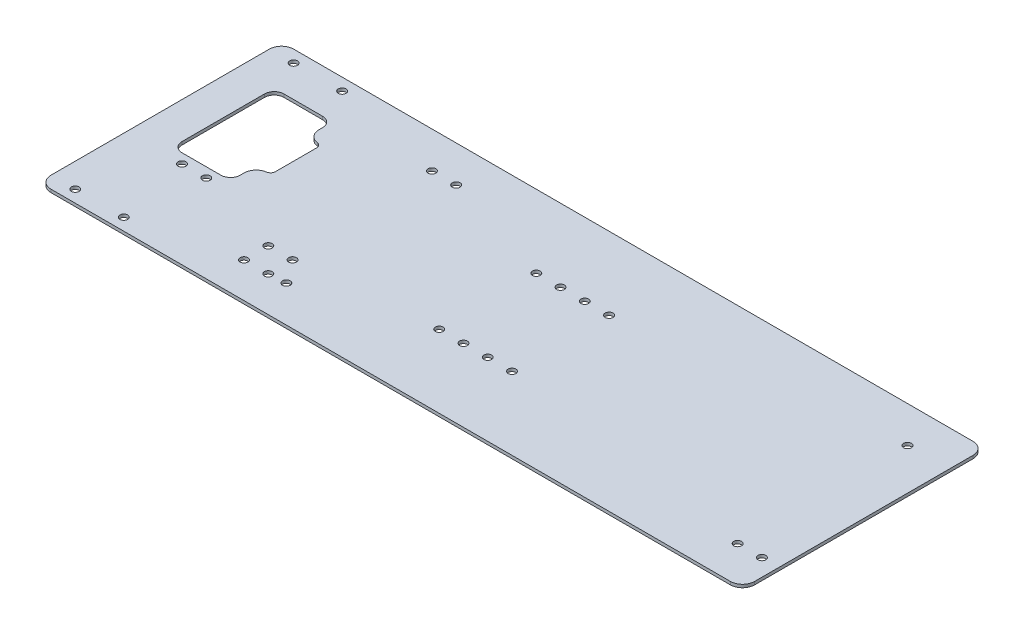
SolidWorks part; units mm, degrees
ref_plane "Front Plane" through (0, 0, 0) normal (0, 0, 1) x (1, 0, 0)
ref_plane "Top Plane" through (0, 0, 0) normal (0, 1, 0) x (1, 0, 0)
ref_plane "Right Plane" through (0, 0, 0) normal (1, 0, 0) x (0, 0, -1)
sketch "Sketch1" plane through (0, 0, 0) normal (0, 1, 0) x (1, 0, 0)
  line L0 (128.27, 0) -> (-128.27, 0) construction
  line L1 (184.15, 63.5) -> (-184.15, 63.5)
  line L2 (184.15, 63.5) -> (184.15, -63.5)
  line L3 (184.15, -63.5) -> (-184.15, -63.5)
  line L4 (-184.15, 63.5) -> (-184.15, -63.5)
  line L5 (184.15, 63.5) -> (-184.15, -63.5) construction
  line L6 (184.15, -63.5) -> (-184.15, 63.5) construction
  line L7 (-128.27, 0) -> (-128.27, 31.75) construction
  line L8 (-128.27, 31.75) -> (-134.62, 31.75) construction
  line L9 (-128.27, 6.35) -> (-134.62, 6.35) construction
  line L12 (-165.1, -12.7) -> (-165.1, 40.64)
  line L15 (-134.62, -12.7) -> (-165.1, -12.7)
  line L17 (-134.62, 40.64) -> (-165.1, 40.64)
  line L18 (0, 63.5) -> (0, -63.5) construction
  line L19 (-134.62, 40.64) -> (-134.62, -12.7)
  line L21 (-95.25, -45.0215) -> (-95.25, -32.3215) construction
  line L22 (-82.55, -45.0215) -> (-95.25, -45.0215) construction
  line L25 (128.27, 31.75) -> (128.27, 6.35) construction
  line L26 (-95.25, -32.3215) -> (-82.55, -32.3215) construction
  line L30 (-82.55, -32.3215) -> (-82.55, -45.0215) construction
  line L31 (184.15, -17.78) -> (154.94, -17.78) construction
  line L32 (146.05, 57.15) -> (184.15, 57.15) construction
  line L33 (154.94, -17.78) -> (142.24, -17.78) construction
  line L34 (146.05, -57.15) -> (184.15, -57.15) construction
  line L35 (-146.05, -57.15) -> (-184.15, -57.15) construction
  line L36 (-146.05, 57.15) -> (-184.15, 57.15) construction
  line L37 (-128.27, 0) -> (-128.27, 6.35) construction
  line L38 (-184.15, -17.78) -> (-154.94, -17.78) construction
  line L39 (-154.94, -17.78) -> (-142.24, -17.78) construction
  line L40 (-134.62, 27.305) -> (-127, 27.305)
  line L41 (-127, 27.305) -> (-127, 0.635)
  line L42 (-127, 0.635) -> (-134.62, 0.635)
  circle A4 centre (171.45, 31.75) radius 2.032 construction
  circle A5 centre (128.27, 31.75) radius 2.032 construction
  circle A6 centre (128.27, 6.35) radius 2.032 construction
  circle A7 centre (171.45, -3.81) radius 2.032 construction
  circle A8 centre (171.45, -57.15) radius 2.032
  circle A9 centre (146.05, -57.15) radius 2.032
  circle A10 centre (171.45, 57.15) radius 2.032
  circle A11 centre (146.05, 57.15) radius 2.032
  circle A12 centre (-146.05, -57.15) radius 2.032
  circle A13 centre (-171.45, -57.15) radius 2.032
  circle A14 centre (-146.05, 57.15) radius 2.032
  circle A15 centre (-171.45, 57.15) radius 2.032
  circle A16 centre (142.24, -17.78) radius 2.032 construction
  circle A17 centre (154.94, -17.78) radius 2.032 construction
  circle A18 centre (-154.94, -17.78) radius 2.032
  circle A19 centre (-142.24, -17.78) radius 2.032
  circle A20 centre (-95.25, -45.0215) radius 2.032
  circle A21 centre (-82.55, -45.0215) radius 2.032
  circle A22 centre (-95.25, -32.3215) radius 2.032
  circle A23 centre (-82.55, -32.3215) radius 2.032
  point P0 (0, 0)
  point P11 (-128.27, 0)
  point P13 (-134.62, 31.75)
  point P17 (-134.62, 6.35)
  point P37 (0, 0)
  point P50 (171.45, 57.15)
  point P51 (146.05, 57.15)
  point P56 (171.45, -57.15)
  point P57 (146.05, -57.15)
  point P84 (-130.81, 27.305)
  point P87 (130.81, 27.305)
  dimension "D5" = 13.335
  dimension "D18" = 4.064
  dimension "D1" = 368.3
  dimension "D2" = 127
  dimension "D3" = 128.27
  dimension "D4" = 25.4
  dimension "D7" = 6.35
  dimension "D8" = 30.48
  dimension "D9" = 53.34
  dimension "D10" = 8.89
  dimension "D11" = 19.05
  dimension "D14" = 12.7
  dimension "D15" = 38.1
  dimension "D16" = 12.7
  dimension "D17" = 38.1
  dimension "D19" = 31.75
  dimension "D20" = 6.35
  dimension "D21" = 6.35
  dimension "D22" = 5.08
  dimension "D23" = 29.21
  dimension "D24" = 12.7
  dimension "D25" = 88.9
  dimension "D26" = 12.7
  dimension "D27" = 7.62
  dimension "D28" = 26.67
  dimension "D29" = 13.335
  dimension "D30" = 18.4785
  dimension "D31" = 12.7
extrude "Boss-Extrude1" add sketch "Sketch1" along normal blind 1.5875 contours L1 L4 L3 L2 A18 A17 A16 A14 A12 A11 A10 A9 A8 L41 L42 L19 L15 L12 L17 L40 A13 A15 A19 | A9 | A8 | A10 | A11 region at (6.2259, 0, 0.5157)
sketch "Sketch2" [suppressed] plane through (0, 1.5875, 0) normal (0, 1, 0) x (1, 0, 0)
  line L0 (-69.85, 63.5) -> (-69.85, -63.5)
  line L1 (184.15, 63.5) -> (-184.15, 63.5) construction
  line L2 (184.15, -63.5) -> (-184.15, -63.5) construction
  circle A0 centre (-82.55, -45.0215) radius 2.032 construction
  circle M9 centre (146.05, 57.15) radius 2.032
  circle M10 centre (171.45, 57.15) radius 2.032
  circle M11 centre (146.05, -57.15) radius 2.032
  circle M12 centre (171.45, -57.15) radius 2.032
  line M13 (184.15, 63.5) -> (-184.15, 63.5)
  line M15 (-184.15, -63.5) -> (184.15, -63.5)
  line M16 (184.15, -63.5) -> (184.15, 63.5)
  dimension "D1" = 12.7
extrude "Cut-Extrude1" [suppressed] cut sketch "Sketch2" against normal through all flip side to cut contours L0 M13 M15 M16 M10 M12 M11 M9
fillet "Fillet1" radius 5.08 4 edges at (-134.62, 0.7937, 12.7) (-165.1, 0.7937, 12.7) (-165.1, 0.7937, -40.64) (-134.62, 0.7937, -40.64)
fillet "Fillet3" radius 6.35 4 edges at (184.15, 0.7937, 63.5) (184.15, 0.7937, -63.5) (-184.15, 0.7937, 63.5) (-184.15, 0.7937, -63.5)
fillet "Fillet4" radius 2.54 2 edges at (-127, 0.7937, -0.635) (-127, 0.7937, -27.305)
fillet "Fillet5" radius 6.35 2 edges at (-134.62, 0.7937, -0.635) (-134.62, 0.7937, -27.305)
fillet "Fillet6" [suppressed] radius 6.35
sketch "Sketch3" plane through (0, 1.5875, 0) normal (0, 1, 0) x (1, 0, 0)
  circle A0 centre (-12.7, -25.4) radius 2.032 construction
  arc A1 (1.9352, -24.7804) -> (1.9352, -26.0196) centre (0, -25.4) ccw construction
  arc A2 (10.7648, -26.0196) -> (10.7648, -24.7804) centre (12.7, -25.4) ccw construction
  circle A3 centre (25.4, -25.4) radius 2.032 construction
  circle A4 centre (25.4, 25.4) radius 2.032 construction
  arc A5 (10.7648, 24.7804) -> (10.7648, 26.0196) centre (12.7, 25.4) ccw construction
  arc A6 (1.9352, 26.0196) -> (1.9352, 24.7804) centre (0, 25.4) ccw construction
  circle A7 centre (-12.7, 25.4) radius 2.032 construction
  circle A8 centre (175.26, -44.45) radius 2.032 construction
  circle A9 centre (162.56, -44.45) radius 2.032 construction
  circle A10 centre (162.56, 44.45) radius 2.032 construction
  circle A11 centre (-73.66, 44.45) radius 2.032 construction
  circle A12 centre (-86.36, 44.45) radius 2.032 construction
  circle A13 centre (-73.66, -44.45) radius 2.032 construction
  circle A14 centre (-12.7, -25.4) radius 2.032
  arc A15 (1.9352, -24.7804) -> (1.9352, -26.0196) centre (0, -25.4) ccw
  arc A16 (10.7648, -26.0196) -> (10.7648, -24.7804) centre (12.7, -25.4) ccw
  circle A17 centre (25.4, -25.4) radius 2.032
  circle A18 centre (25.4, 25.4) radius 2.032
  arc A19 (10.7648, 24.7804) -> (10.7648, 26.0196) centre (12.7, 25.4) ccw
  arc A20 (1.9352, 26.0196) -> (1.9352, 24.7804) centre (0, 25.4) ccw
  circle A21 centre (-12.7, 25.4) radius 2.032
  circle A22 centre (175.26, -44.45) radius 2.032
  circle A23 centre (162.56, -44.45) radius 2.032
  circle A24 centre (162.56, 44.45) radius 2.032
  circle A25 centre (-73.66, 44.45) radius 2.032
  circle A26 centre (-86.36, 44.45) radius 2.032
  circle A27 centre (-73.66, -44.45) radius 2.032
  circle A28 centre (0, -25.4) radius 2.032
  circle A29 centre (12.7, -25.4) radius 2.032
  circle A30 centre (0, 25.4) radius 2.032
  circle A31 centre (12.7, 25.4) radius 2.032
extrude "Cut-Extrude5" cut sketch "Sketch3" against normal through all contours A26 | A24 | A15 A28 | A16 A29 | A20 A30 | A19 A31 | A27 | A25 | A21 | A14 | A17 | A18 | A23 | A22 region at (0, 1.5875, 25.4) region at (12.7, 1.5875, 25.4) region at (12.7, 1.5875, -25.4) region at (0, 1.5875, -25.4) region at (162.56, 1.5875, -44.45) region at (-86.36, 1.5875, -44.45)
equation "\".80.55in\"=0.55"
